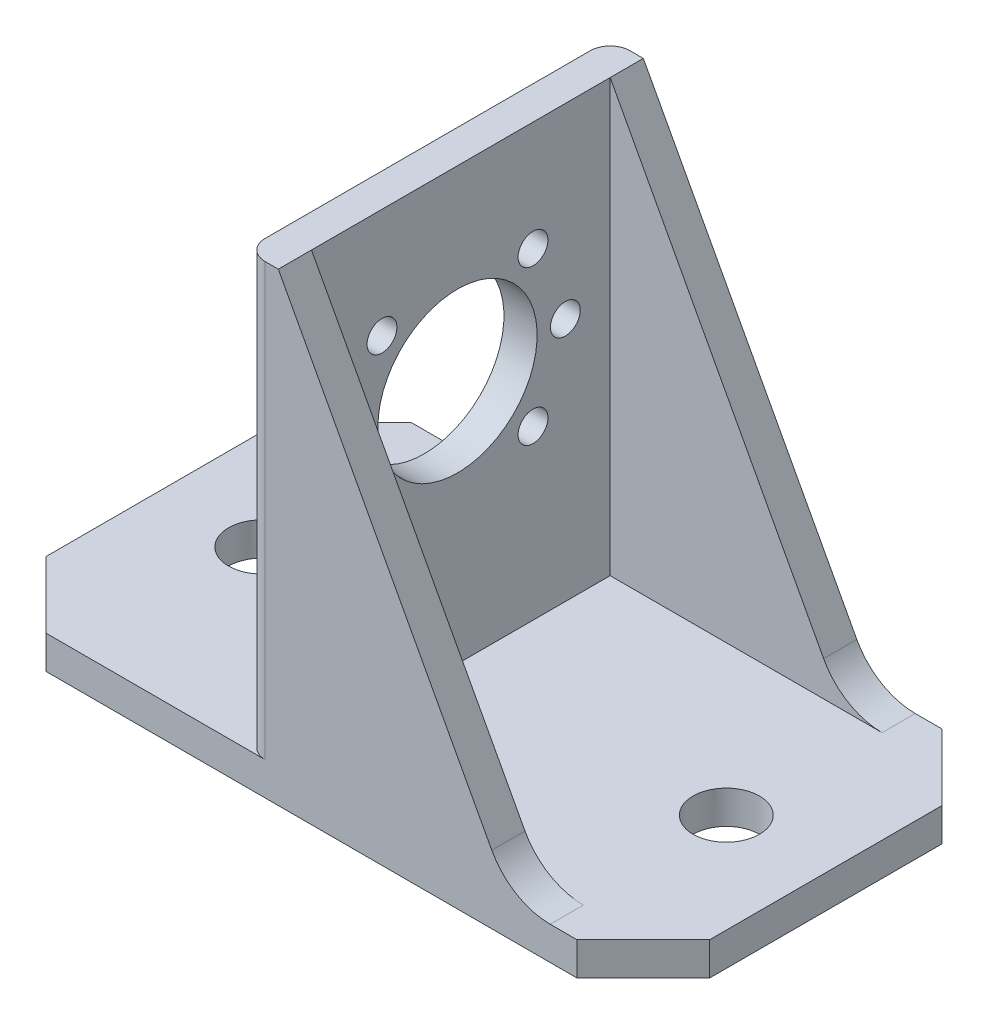
SolidWorks part; units mm, degrees
ref_plane "Alzado" through (0, 0, 0) normal (0, 0, 1) x (1, 0, 0)
ref_plane "Planta" through (0, 0, 0) normal (0, 1, 0) x (1, 0, 0)
ref_plane "Vista lateral" through (0, 0, 0) normal (1, 0, 0) x (0, 0, -1)
sketch "Croquis1" plane through (0, 0, 0) normal (0, 1, 0) x (1, 0, 0)
  line L1 (-50, -27.5) -> (50, -27.5)
  line L2 (-50, -27.5) -> (-50, 27.5)
  line L3 (-50, 27.5) -> (50, 27.5)
  line L4 (50, -27.5) -> (50, 27.5)
  line L5 (-50, -27.5) -> (50, 27.5) construction
  line L6 (-50, 27.5) -> (50, -27.5) construction
  point P0 (0, 0)
  dimension "D1" = 55
  dimension "D2" = 100
extrude "Saliente-Extruir1" add sketch "Croquis1" along normal blind 5
sketch "Croquis2" plane through (0, 5, 0) normal (0, 1, 0) x (1, 0, 0)
  line L0 (0, 27.5) -> (0, -27.5) construction
  line L1 (50, 27.5) -> (-50, 27.5) construction
  line L2 (-50, -27.5) -> (50, -27.5) construction
  line L3 (-35, 0) -> (35, 0) construction
  circle A0 centre (35, 0) radius 5
  circle A1 centre (-35, 0) radius 5
  point P9 (0, 0)
  dimension "D1" = 10
  dimension "D2" = 70
extrude "Cortar-Extruir1" cut sketch "Croquis2" against normal up to surface (5 mm away) up to face at (0, 0, 0)
sketch "Croquis3" plane through (0, 5, 0) normal (0, 1, 0) x (1, 0, 0)
  line L0 (30, 27.5) -> (-7, 27.5)
  line L1 (50, 27.5) -> (-50, 27.5) construction
  line L2 (-10, 24.5) -> (-10, -24.5)
  line L3 (-50, -27.5) -> (50, -27.5) construction
  line L4 (-7, -27.5) -> (30, -27.5)
  line L5 (30, 22.5) -> (-5, 22.5)
  line L6 (-5, 22.5) -> (-5, -22.5)
  line L7 (-5, -22.5) -> (30, -22.5)
  line L8 (30, 27.5) -> (30, 22.5)
  line L9 (30, -22.5) -> (30, -27.5)
  arc A0 (-10, -24.5) -> (-7, -27.5) centre (-7, -24.5) ccw
  arc A1 (-7, 27.5) -> (-10, 24.5) centre (-7, 24.5) ccw
  arc A2 (-5, 22.5) -> (-5, 22.5) centre (-5, 22.5) ccw
  arc A3 (-5, -22.5) -> (-5, -22.5) centre (-5, -22.5) ccw
  point P9 (0, 0)
  point P12 (-10, -27.5)
  point P15 (-10, 27.5)
  dimension "D3" = 3
  dimension "D1" = 40
  dimension "D2" = 10
  dimension "D4" = 5
extrude "Saliente-Extruir2" add sketch "Croquis3" along normal blind 65
sketch "Croquis4" plane through (0, 0, 27.5) normal (0, 0, 1) x (1, 0, 0)
  line L0 (-5, 70) -> (-5, 5) construction
  line L1 (-5, 70) -> (-5, 5) construction
  line L2 (-5, 70) -> (30, 5)
  line L3 (30, 5) -> (30, 70)
  line L4 (30, 70) -> (-5, 70)
extrude "Cortar-Extruir2" cut sketch "Croquis4" against normal up to surface (55 mm away) up to face at (5.75, 20, -27.5)
chamfer "Chaflán1" distance 10 angle 45 4 edges at (50, 2.5, 27.5) (50, 2.5, -27.5) (-50, 2.5, -27.5) (-50, 2.5, 27.5)
fillet "Redondeo1" radius 10 2 edges at (30, 5, 25) (30, 5, -25)
sketch "Croquis5" plane through (-10, 0, 0) normal (-1, 0, 0) x (0, 0, 1)
  circle A0 centre (0.5, 41.9) radius 12 construction
  circle A1 centre (0.5, 41.9) radius 12
  circle A2 centre (-15.75, 41.9) radius 2.25 construction
  circle A3 centre (-15.75, 41.9) radius 2.25 construction
  circle A4 centre (-10.8799, 30.3) radius 2.25 construction
  circle A5 centre (11.8799, 30.3) radius 2.25 construction
  circle A6 centre (16.75, 41.9) radius 2.25 construction
  circle A7 centre (11.8799, 53.5) radius 2.25 construction
  circle A8 centre (-15.75, 41.9) radius 2.25
  circle A9 centre (-15.75, 41.9) radius 2.25
  circle A10 centre (-10.8799, 30.3) radius 2.25
  circle A11 centre (11.8799, 30.3) radius 2.25
  circle A12 centre (16.75, 41.9) radius 2.25
  circle A13 centre (11.8799, 53.5) radius 2.25
  circle A14 centre (-10.8799, 53.5) radius 2.25 construction
  circle A15 centre (-10.8799, 53.5) radius 2.25
extrude "Cortar-Extruir3" cut sketch "Croquis5" against normal up to surface (5 mm away) contours A1 | A11 | A12 | A13 | A10 | A8 | A15 region at (-10, 41.9, 0.5) region at (-10, 41.9, -15.75) region at (-10, 30.3, -10.8799) region at (-10, 30.3, 11.8799) region at (-10, 41.9, 16.75) region at (-10, 53.5, 11.8799) region at (-10, 53.5, -10.8799) up to face at (-5, 37.5, 0)
